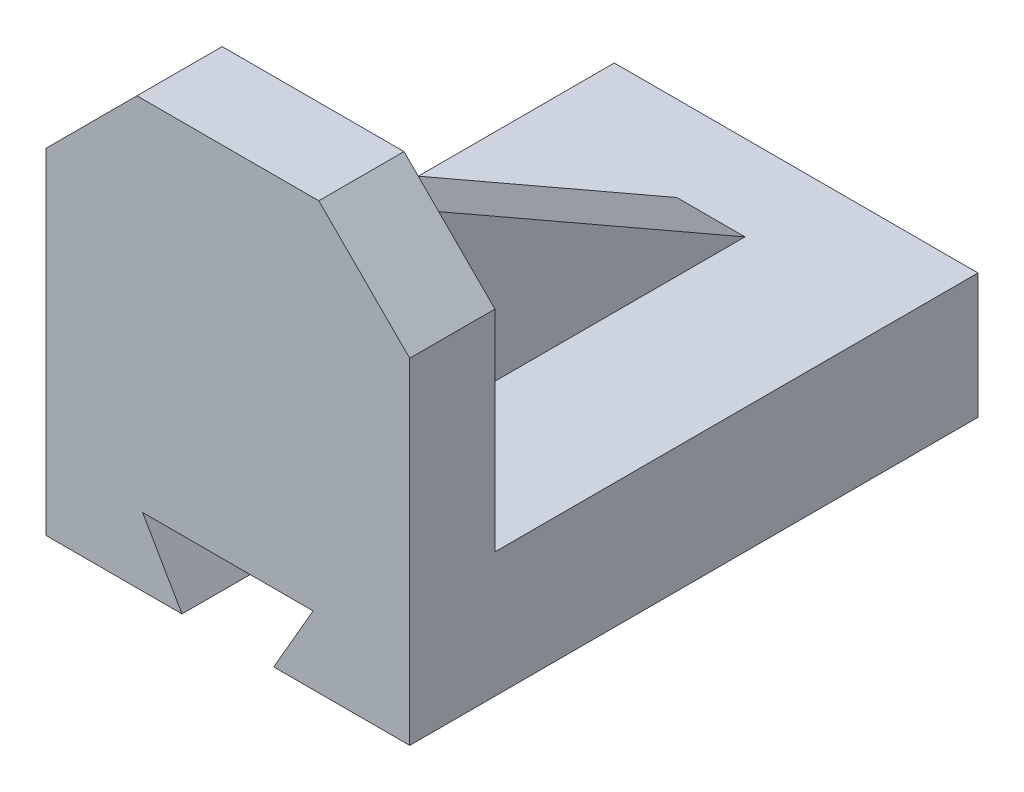
SolidWorks part; units mm, degrees
ref_plane "Front Plane" through (0, 0, 0) normal (0, 0, 1) x (1, 0, 0)
ref_plane "Top Plane" through (0, 0, 0) normal (0, 1, 0) x (1, 0, 0)
ref_plane "Right Plane" through (0, 0, 0) normal (1, 0, 0) x (0, 0, -1)
sketch "Sketch2" plane through (0, 0, 0) normal (1, 0, 0) x (0, 0, -1)
  line L0 (0, 0) -> (85, 0)
  line L1 (85, 0) -> (85, -22)
  line L2 (85, -22) -> (-15, -22)
  line L3 (-15, -22) -> (-15, 53)
  line L4 (-15, 53) -> (0, 53)
  line L5 (0, 53) -> (0, 0)
  line L6 (0, 0) -> (0, 40)
  line L7 (0, 40) -> (70, 0)
  line L8 (70, 0) -> (0, 0)
  dimension "D1" = 100
  dimension "D2" = 75
  dimension "D3" = 15
  dimension "D4" = 22
  dimension "D5" = 40
  dimension "D6" = 70
extrude "Boss-Extrude3" add sketch "Sketch2" along normal mid plane 64 contours L5 L4 L3 L2 L1 L0 region at (0, -1.0459, -23.7187)
extrude "Boss-Extrude4" add sketch "Sketch2<5>" along normal mid plane 12 contours L7 L5 L0 region at (0, 13.3333, -23.3333)
sketch "Sketch2<5>" plane through (0, 0, 0) normal (1, 0, 0) x (0, 0, -1) same geometry as "Sketch2"
sketch "Sketch5" plane through (0, 0, 0) normal (0, 0, 1) x (1, 0, 0)
  line L0 (16, 53) -> (32, 37)
  line L1 (32, 53) -> (-32, 53) construction
  line L2 (32, 53) -> (32, 0) construction
  line L3 (32, 37) -> (32, 53)
  line L4 (32, 53) -> (16, 53)
  line L5 (-32, 53) -> (-32, 37)
  line L6 (-32, 53) -> (-32, 0) construction
  line L7 (-32, 37) -> (-16, 53)
  line L8 (-16, 53) -> (-32, 53)
  line L9 (8.0718, -22) -> (15, -10)
  line L10 (32, -22) -> (-32, -22) construction
  line L11 (15, -10) -> (-15, -10)
  line L12 (-15, -10) -> (-8.0718, -22)
  line L13 (-8.0718, -22) -> (8.0718, -22)
  line L14 (15, -10) -> (32, -10)
  line L15 (32, 0) -> (32, -22) construction
  line L16 (32, -10) -> (-32, -10)
  line L17 (-32, 0) -> (-32, -22) construction
  dimension "D1" = 16
  dimension "D2" = 16
  dimension "D3" = 16
  dimension "D4" = 16
  dimension "D5" = 17
  dimension "D6" = 17
  dimension "D7" = 12
  dimension "D8" = 60
  dimension "D9" = 60
extrude "Cut-Extrude1" cut sketch "Sketch5" against normal through all both and the other way through all contours L12 L13 L9 L11 region at (0, -15.3994, 0)
extrude "Cut-Extrude2" cut sketch "Sketch5<3>" against normal through all and the other way through all contours L3 L4 L0 | L7 L8 L5 region at (26.6667, 47.6667, 0) region at (-26.6667, 47.6667, 0)
sketch "Sketch5<3>" plane through (0, 0, 0) normal (0, 0, 1) x (1, 0, 0) same geometry as "Sketch5"
